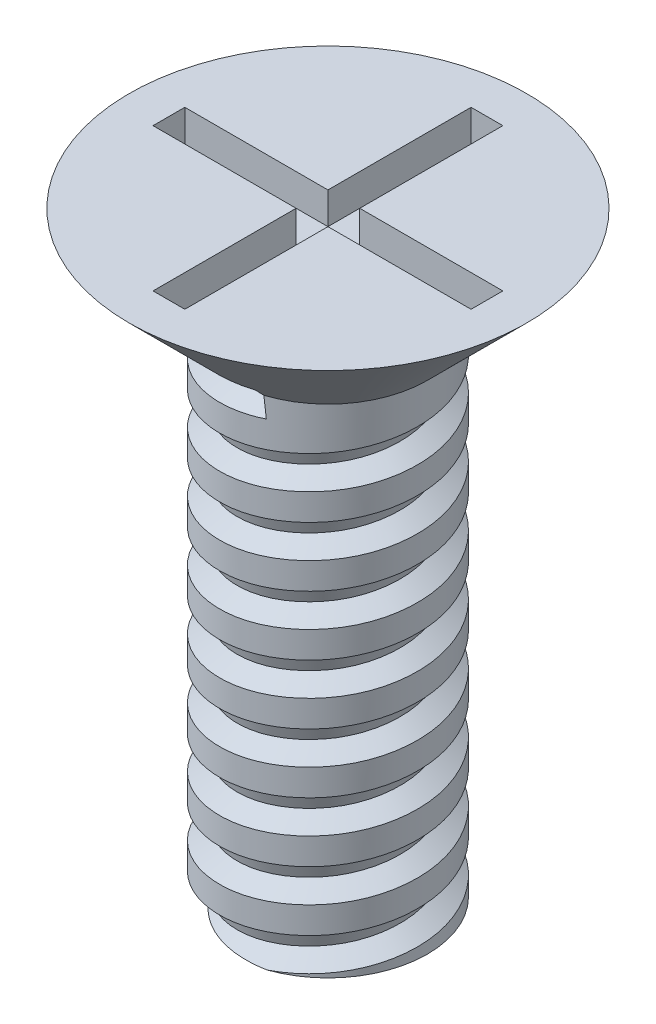
SolidWorks part; units mm, degrees
ref_plane "Front Plane" through (0, 0, 0) normal (0, 0, 1) x (1, 0, 0)
ref_plane "Top Plane" through (0, 0, 0) normal (0, 1, 0) x (1, 0, 0)
ref_plane "Right Plane" through (0, 0, 0) normal (1, 0, 0) x (0, 0, -1)
sketch "Sketch1" plane through (0, 0, 0) normal (0, 1, 0) x (1, 0, 0)
  circle A0 centre (0, 0) radius 5
  dimension "D1" = 10
extrude "Boss-Extrude5" add sketch "Sketch1" along normal blind 15
sketch "Sketch4" plane through (0, 0, 0) normal (0, -1, 0) x (1, 0, 0)
  circle A0 centre (0, 0) radius 2.5
  circle A1 centre (0, 0) radius 5
  dimension "D1" = 5
extrude "Cut-Extrude2" cut sketch "Sketch4" against normal blind 12
chamfer "Chamfer7" distance 3 angle 45 1 edges at (0, 12, -5)
sketch "Sketch5" plane through (0, 15, 0) normal (0, 1, 0) x (1, 0, 0)
  line L0 (0, 0) -> (0, 4)
  line L1 (0, 0) -> (0, -4)
  line L2 (0, -4) -> (-0.4, -4)
  line L3 (0, 4) -> (0.4, 4)
  line L5 (-0.4, -4) -> (0.4, -4)
  line L6 (-0.4, -4) -> (-0.4, 4)
  line L7 (-0.4, 4) -> (0.4, 4)
  line L8 (0.4, -4) -> (0.4, 4)
  dimension "D1" = 0.4
  dimension "D2" = 0.4
extrude "Cut-Extrude3" cut sketch "Sketch5" against normal blind 0.8 contours L6 L5 L8 L7
sketch "Sketch6" plane through (0, 15, 0) normal (0, 1, 0) x (1, 0, 0)
  line L0 (0, 0) -> (-4, 0)
  line L1 (0, 0) -> (4, 0)
  line L2 (-4, 0) -> (-4, 0.4)
  line L3 (4, 0) -> (4, -0.4)
  line L5 (-4, 0.4) -> (4, 0.4)
  line L6 (-4, 0.4) -> (-4, -0.4)
  line L7 (-4, -0.4) -> (4, -0.4)
  line L8 (4, 0.4) -> (4, -0.4)
  dimension "D1" = 4
  dimension "D2" = 4
  dimension "D3" = 0.4
  dimension "D4" = 0.4
extrude "Cut-Extrude5" cut sketch "Sketch6" against normal blind 0.8 contours L5 L2 L0 L6 | L6 L7 L0 | L8 L5 L1 | L8 L7 L3 L1
sketch "Sketch16" plane through (0, 0, 0) normal (0, -1, 0) x (1, 0, 0)
  circle A0 centre (0, 0) radius 2.5
curve "Helix/Spiral2" pitch 1.5 height 12.45 turns 8.3
ref_plane "Plane7" through (0.7725, 12.45, 2.3776) normal (0.9467, 0.0951, -0.3076) x (-0.3061, -0.0307, -0.9515)
sketch "Sketch17" plane through (0.7725, 12.45, 2.3776) normal (0.9467, 0.0951, -0.3076) x (-0.3061, -0.0307, -0.9515)
  line L1 (0, -0.4635) -> (0.4408, -0.1432)
  line L2 (0.4408, -0.1432) -> (0.2725, 0.375)
  line L3 (0.2725, 0.375) -> (-0.2725, 0.375)
  line L4 (-0.2725, 0.375) -> (-0.4408, -0.1432)
  line L5 (-0.4408, -0.1432) -> (0, -0.4635)
  circle A0 centre (0, 0) radius 0.375 construction
sweep "Cut-Sweep7" cut profiles "Sketch17" path "Helix/Spiral2" align with end faces yes
